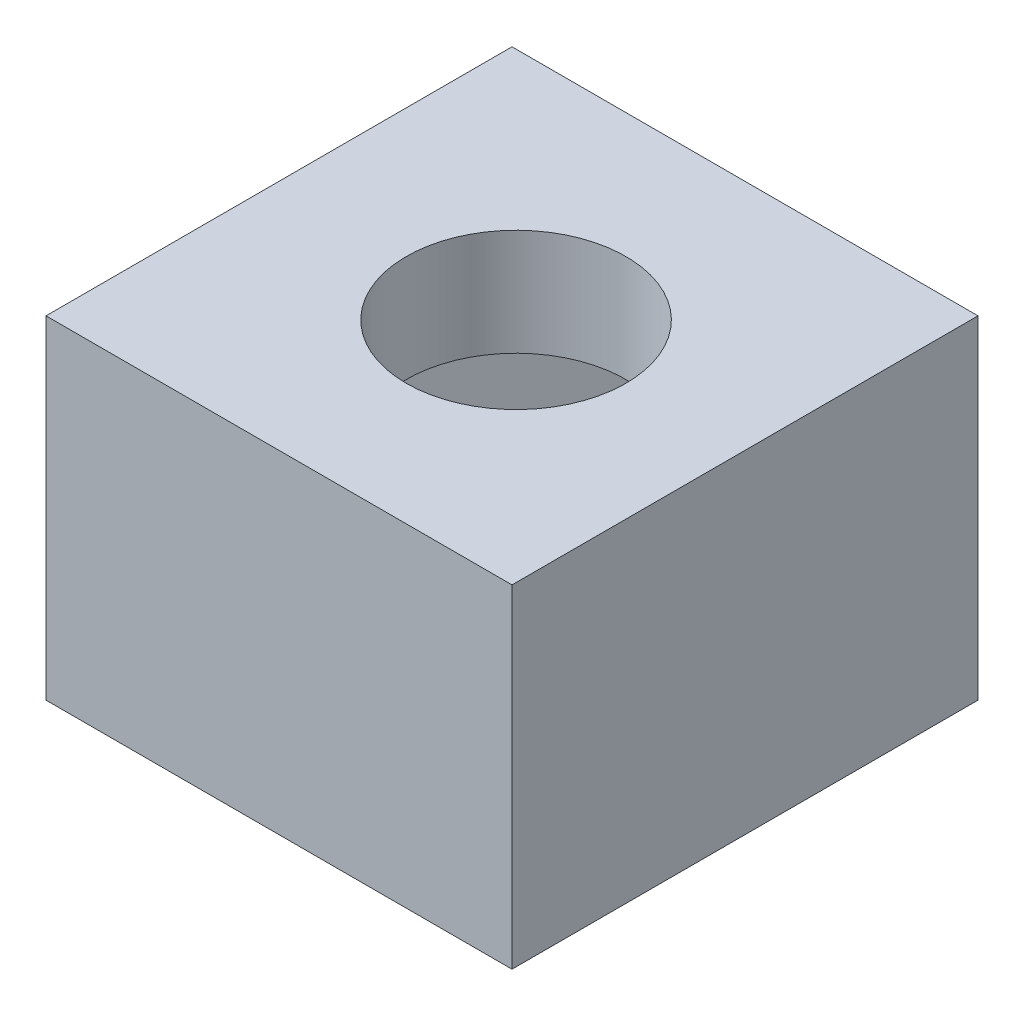
SolidWorks part; units mm, degrees
ref_plane "Front Plane" through (0, 0, 0) normal (0, 0, 1) x (1, 0, 0)
ref_plane "Top Plane" through (0, 0, 0) normal (0, 1, 0) x (1, 0, 0)
ref_plane "Right Plane" through (0, 0, 0) normal (1, 0, 0) x (0, 0, -1)
sketch "Sketch1" plane through (0, 0, 0) normal (0, 1, 0) x (1, 0, 0)
  line L1 (-4.1778, 1.3717) -> (2.8222, 1.3717)
  line L2 (-4.1778, 1.3717) -> (-4.1778, -5.6283)
  line L3 (-4.1778, -5.6283) -> (2.8222, -5.6283)
  line L4 (2.8222, 1.3717) -> (2.8222, -5.6283)
  dimension "D1" = 7
  dimension "D2" = 7
extrude "Boss-Extrude1" add sketch "Sketch1" along normal blind 5
sketch "Sketch4" plane through (0, 5, 0) normal (0, 1, 0) x (1, 0, 0)
  line L1 (-1.416, 0.9165) -> (-3.6614, -1.3288)
  line L2 (-3.6614, -1.3288) -> (-2.8395, -4.3961)
  line L3 (-2.8395, -4.3961) -> (0.2277, -5.2179)
  line L4 (0.2277, -5.2179) -> (2.4731, -2.9726)
  line L5 (2.4731, -2.9726) -> (1.6512, 0.0947)
  line L6 (1.6512, 0.0947) -> (-1.416, 0.9165)
  circle A0 centre (-0.5941, -2.1507) radius 1.65
  circle A1 centre (-0.5941, -2.1507) radius 2.75 construction
  dimension "D1" = 5.5
extrude "Cut-Extrude4" cut sketch "Sketch4" against normal blind 4
sketch "Sketch6" plane through (0, 5, 0) normal (0, 1, 0) x (1, 0, 0)
  line L1 (-3.6614, -1.3288) -> (-2.8395, -4.3961)
  line L2 (-2.8395, -4.3961) -> (0.2277, -5.2179)
  line L3 (0.2277, -5.2179) -> (2.4731, -2.9726)
  line L4 (2.4731, -2.9726) -> (1.6512, 0.0947)
  line L5 (1.6512, 0.0947) -> (-1.416, 0.9165)
  line L6 (-1.416, 0.9165) -> (-3.6614, -1.3288)
  circle A0 centre (-0.5941, -2.1507) radius 1.65
  circle A1 centre (-0.5941, -2.1507) radius 2.75 construction
  circle A2 centre (-0.5941, -2.1507) radius 1.65
  circle M2 centre (-0.5941, -2.1507) radius 1.65
  dimension "D1" = 5.5
extrude "Cut-Extrude6" cut sketch "Sketch6" against normal blind 4 contours M2 region at (-0.5941, 5, 2.1507)
extrude "Boss-Extrude2" add sketch "Sketch6<4>" against normal blind 1.6 contours L5 L6 L1 L2 L3 L4 M2 region at (-2.4773, 5, 0.2675)
sketch "Sketch6<4>" plane through (0, 5, 0) normal (0, 1, 0) x (1, 0, 0) same geometry as "Sketch6"
